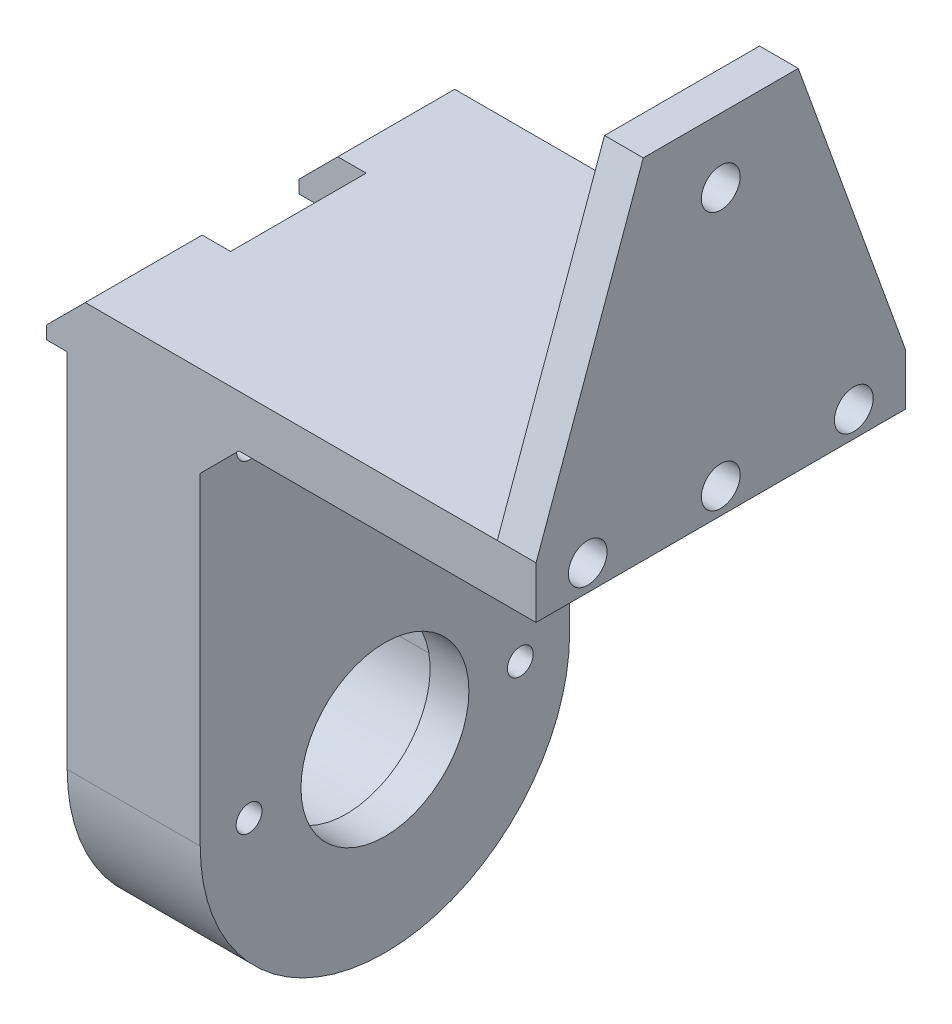
SolidWorks part; units mm, degrees
ref_plane "前视基准面" through (0, 0, 0) normal (0, 0, 1) x (1, 0, 0)
ref_plane "上视基准面" through (0, 0, 0) normal (0, 1, 0) x (1, 0, 0)
ref_plane "右视基准面" through (0, 0, 0) normal (1, 0, 0) x (0, 0, -1)
sketch "Model" plane through (0, 0, 0) normal (0, 0, 1) x (1, 0, 0)
  line L0 (-24.9788, -17.9232) -> (-14.6788, -17.9232)
  line L1 (-24.9788, 24.3768) -> (-24.9788, -17.9232)
  line L2 (-14.6788, 21.3768) -> (-14.6788, -17.9232)
  line L3 (11.3212, 51.3768) -> (11.3212, 24.3768)
  line L4 (11.3212, 24.3768) -> (-11.6788, 24.3768)
  line L5 (-14.6788, 21.3768) -> (-11.6788, 24.3768)
  line L6 (-26.5788, 24.3768) -> (-24.9788, 24.3768)
  line L7 (8.3212, 51.3768) -> (11.3212, 51.3768)
  line L8 (8.3212, 51.3768) -> (8.3212, 28.3768)
  line L9 (5.3212, 46.3768) -> (14.3212, 46.3768) construction
  line L10 (-17.6788, -10.1232) -> (-14.6788, -10.1232)
  line L11 (-17.6788, 2.8768) -> (-14.6788, 2.8768)
  line L12 (-17.6788, -11.1032) -> (-24.9788, -11.1032)
  line L13 (-17.6788, 21.3768) -> (-24.9788, 21.3768)
  line L14 (-22.9788, 28.3768) -> (-22.9788, 21.3768)
  line L15 (-17.6788, 21.3768) -> (-17.6788, -11.1032)
  line L16 (-26.5788, 25.3768) -> (-23.5788, 28.3768)
  line L17 (-26.5788, 24.3768) -> (-26.5788, 25.3768)
  line L18 (-23.5788, 28.3768) -> (8.3212, 28.3768)
  dimension "D1" = 4
extrude "凸台-拉伸1" add sketch "Model" along normal blind 28.6 contours L9 L8 L18 L14 L13 L15 L11 L2 L5 L4 L3 | L11 L15 L10 L2 | L10 L15 L12 L1 L0 L2 | L1 L0 L2 L5 L4 L3 L7 L8 L18 L16 L17 L6 region at (-19.6822, -14.3565, 0) region at (-16.1788, -3.6232, 0) region at (-6.1488, 25.2992, 0)
sketch "草图2" plane through (-24.9788, 0, 0) normal (-1, 0, 0) x (0, 0, 1)
  line L0 (28.6, 24.3768) -> (0, 24.3768) construction
  line L1 (28.6, 24.3768) -> (28.6, -17.9232) construction
  line L2 (0, 24.3768) -> (0, -17.9232) construction
  circle A0 centre (3.78, 21.3768) radius 1
  circle A1 centre (24.78, 21.3768) radius 1
  circle A2 centre (24.82, -3.6232) radius 1
  circle A3 centre (3.82, -3.6232) radius 1
  dimension "D1" = 3
  dimension "D2" = 3
  dimension "D3" = 21
  dimension "D4" = 2
  dimension "D5" = 21
  dimension "D6" = 25
  dimension "D7" = 25
  dimension "D8" = 2
  dimension "D9" = 2
  dimension "D10" = 2
  dimension "D11" = 3.78
  dimension "D12" = 3.82
  dimension "D13" = 3.78
  dimension "D14" = 3.82
extrude "切除-拉伸1" cut sketch "草图2" against normal blind 28.6
fillet "圆角1" radius 14.3 2 edges at (-19.8288, -17.9232, 28.6) (-19.8288, -17.9232, 0)
sketch "草图3" plane through (-24.9788, 0, 0) normal (-1, 0, 0) x (0, 0, 1)
  line L0 (21.8, -3.6232) -> (21.8, 19.8768)
  line L1 (20.3, 21.3768) -> (8.3, 21.3768)
  line L2 (6.8, 19.8768) -> (6.8, -3.6232)
  arc A0 (6.8, -3.6232) -> (21.8, -3.6232) centre (14.3, -3.6232) ccw
  arc A1 (8.3, 21.3768) -> (6.8, 19.8768) centre (8.3, 19.8768) ccw
  arc A2 (21.8, 19.8768) -> (20.3, 21.3768) centre (20.3, 19.8768) ccw
  point P10 (21.8, 21.3768)
  dimension "D1" = 7.5
  dimension "D3" = 1.5
  dimension "D2" = 25
extrude "切除-拉伸2" cut sketch "草图3" against normal blind 7.3
sketch "草图4" plane through (-24.9788, 0, 0) normal (-1, 0, 0) x (0, 0, 1)
  line L0 (9.05, 36.9492) -> (9.05, 14.6824)
  line L1 (9.05, 14.6824) -> (19.55, 14.6824)
  line L2 (19.55, 14.6824) -> (19.55, 36.9492)
  line L3 (19.55, 36.9492) -> (9.05, 36.9492)
  line L4 (28.6, 51.3768) -> (0, 51.3768) construction
  point P0 (14.3, 51.3768)
  dimension "D1" = 10.5
  dimension "D2" = 5.25
extrude "切除-拉伸4" cut sketch "草图4" against normal blind 3.6 and the other way blind 19.6
sketch "草图5" plane through (-17.6788, 0, 0) normal (-1, 0, 0) x (0, 0, 1)
  circle A0 centre (14.3, -3.6232) radius 6.5
  dimension "D1" = 13
extrude "切除-拉伸5" cut sketch "草图5" against normal blind 3.6
sketch "草图6" plane through (11.3212, 0, 0) normal (1, 0, 0) x (0, 0, -1)
  line L1 (-28.6, 51.3768) -> (-28.6, 24.3768) construction
  line L2 (0, 51.3768) -> (0, 24.3768) construction
  line L3 (0, 28.3768) -> (-8.3, 51.3768)
  line L4 (-28.6, 51.3768) -> (0, 51.3768) construction
  line L6 (-20.3, 51.3768) -> (-28.6, 28.3768)
  line L7 (-28.6, 28.3768) -> (-35.2648, 54.9015)
  line L8 (-35.2648, 54.9015) -> (-20.3, 51.3768)
  line L9 (-8.3, 51.3768) -> (5.7279, 54.9015)
  line L10 (5.7279, 54.9015) -> (0, 28.3768)
  dimension "D1" = 12
  dimension "D3" = 8.3
extrude "切除-拉伸6" cut sketch "草图6" against normal blind 22.6
sketch "草图7" plane through (11.3212, 0, 0) normal (1, 0, 0) x (0, 0, -1)
  line L0 (-14.3, 51.3768) -> (-14.3, 18.6333) construction
  line L1 (-20.3, 51.3768) -> (-8.3, 51.3768) construction
  line L2 (-28.6, 24.3768) -> (0, 24.3768) construction
  line L3 (-28.6, 24.3768) -> (0, 24.3768) construction
  circle A0 centre (-14.3, 46.3768) radius 1.5
  circle A1 centre (-24.6, 26.3768) radius 1.5
  circle A2 centre (-14.3, 26.3768) radius 1.5
  circle A3 centre (-4, 26.3768) radius 1.5
  dimension "D1" = 10.3
  dimension "D2" = 10.3
  dimension "D3" = 0
  dimension "D4" = 3
  dimension "D5" = 3
  dimension "D6" = 3
  dimension "D7" = 2
  dimension "D8" = 2
  dimension "D9" = 2
  dimension "D10" = 3
  dimension "D12" = 5
  dimension "D11" = 0
extrude "切除-拉伸7" cut sketch "草图7" against normal blind 8
